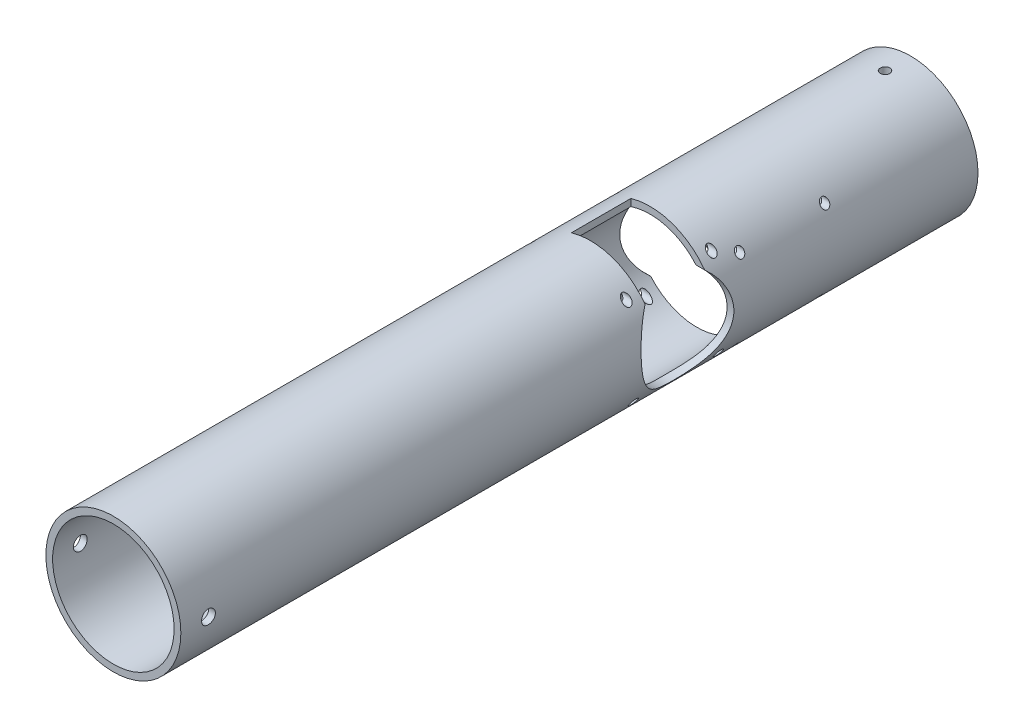
SolidWorks part; units mm, degrees
material "6061 Alloy"
ref_plane "Front Plane" through (0, 0, 0) normal (0, 0, 1) x (1, 0, 0)
ref_plane "Top Plane" through (0, 0, 0) normal (0, 1, 0) x (1, 0, 0)
ref_plane "Right Plane" through (0, 0, 0) normal (1, 0, 0) x (0, 0, -1)
sketch "Sketch1" plane through (0, 0, 0) normal (0, 0, 1) x (1, 0, 0)
  circle A0 centre (0, 0) radius 31.75
  circle A1 centre (0, 0) radius 28.575
  dimension "D1" = 63.5
  dimension "D2" = 57.15
extrude "Boss-Extrude1" add sketch "Sketch1" along normal blind 125 and the other way blind 250 contours A1 | A0 region at (0, 0, 0)
sketch "Sketch2" plane through (0, 0, 0) normal (1, 0, 0) x (0, 0, -1)
  circle A2 centre (163.488, -2) radius 21.75
  dimension "D1" = 43.5
  dimension "D2" = 163.488
  dimension "D3" = 2
extrude "Cut-Extrude1" cut sketch "Sketch2" against normal through all
sketch "Sketch3" plane through (0, 0, 0) normal (1, 0, 0) x (0, 0, -1)
  circle A1 centre (113.45, 2) radius 21.75
  dimension "D1" = 113.45
  dimension "D2" = 43.5
  dimension "D3" = 2
extrude "Cut-Extrude2" cut sketch "Sketch3" along normal through all
sketch "Sketch5" plane through (0, 0, 0) normal (1, 0, 0) x (0, 0, -1)
  line L1 (177.488, -12.75) -> (149.488, -12.75)
  line L2 (177.488, -12.75) -> (177.488, -34.75)
  line L3 (177.488, -34.75) -> (149.488, -34.75)
  line L4 (149.488, -12.75) -> (149.488, -34.75)
  line L5 (177.488, -12.75) -> (149.488, -34.75) construction
  line L6 (177.488, -34.75) -> (149.488, -12.75) construction
  circle A0 centre (163.488, -2) radius 21.75 construction
  circle A1 centre (163.488, -2) radius 21.75 construction
  point P0 (163.488, -23.75)
  dimension "D1" = 28
  dimension "D2" = 22
  dimension "D3" = 163.488
extrude "Cut-Extrude4" cut sketch "Sketch5" against normal through all from offset 9
sketch "Sketch6" plane through (0, 0, 0) normal (1, 0, 0) x (0, 0, -1)
  line L1 (99.45, 34.75) -> (127.45, 34.75)
  line L2 (99.45, 34.75) -> (99.45, 12.75)
  line L3 (99.45, 12.75) -> (127.45, 12.75)
  line L4 (127.45, 34.75) -> (127.45, 12.75)
  line L5 (99.45, 34.75) -> (127.45, 12.75) construction
  line L6 (99.45, 12.75) -> (127.45, 34.75) construction
  circle A0 centre (113.45, 2) radius 21.75 construction
  circle A1 centre (113.45, 2) radius 21.75 construction
  point P0 (113.45, 23.75)
  dimension "D1" = 28
  dimension "D2" = 22
  dimension "D3" = 113.45
extrude "Cut-Extrude5" cut sketch "Sketch6" along normal through all from offset 9 offset against normal yes
sketch "Sketch10" plane through (0, 0, 0) normal (1, 0, 0) x (0, 0, -1)
  line L1 (203.488, 38) -> (123.488, 38)
  line L2 (203.488, 38) -> (203.488, -42)
  line L3 (203.488, -42) -> (123.488, -42)
  line L4 (123.488, 38) -> (123.488, -42)
  line L5 (203.488, 38) -> (123.488, -42) construction
  line L6 (203.488, -42) -> (123.488, 38) construction
  point P0 (163.488, -2)
  dimension "D1" = 80
  dimension "D2" = 80
sketch "Sketch11" plane through (0, 0, 0) normal (1, 0, 0) x (0, 0, -1)
  line L0 (203.488, 38) -> (123.488, -42) construction
  line L1 (203.488, -42) -> (123.488, 38) construction
  circle A0 centre (183.488, 18) radius 2
  circle A1 centre (143.488, 18) radius 2
  circle A2 centre (143.488, -22) radius 2
  circle A3 centre (183.488, -22) radius 2
  dimension "D5" = 4
  dimension "D6" = 4
  dimension "D7" = 4
  dimension "D8" = 4
  dimension "D1" = 20
  dimension "D2" = 20
  dimension "D3" = 20
  dimension "D4" = 20
extrude "Cut-Extrude8" cut sketch "Sketch11" against normal through all both and the other way through all
sketch "Sketch12" plane through (0, 0, 0) normal (1, 0, 0) x (0, 0, -1)
  line L1 (-125, 31.75) -> (-125, -31.75) construction
  circle A0 centre (-136, 0) radius 3.25
  circle A1 centre (-112, 0) radius 3.25
  dimension "D1" = 6.5
  dimension "D2" = 6.5
  dimension "D3" = 24
  dimension "D4" = 13
extrude "Cut-Extrude10" cut sketch "Sketch12" against normal through all both and the other way through all
sketch "Sketch13" plane through (0, 0, 0) normal (0, 1, 0) x (1, 0, 0)
  line L0 (0, -55) -> (0, 55) construction
  line L1 (28.575, 250) -> (-28.575, 250) construction
  circle A0 centre (0, 238) radius 2.25
  dimension "D2" = 4.5
  dimension "D1" = 12
extrude "Cut-Extrude11" cut sketch "Sketch13" against normal through all both and the other way through all
sketch "Sketch14" plane through (0, 0, 0) normal (1, 0, 0) x (0, 0, -1)
  line L1 (88.45, 27) -> (138.45, 27)
  line L2 (88.45, 27) -> (88.45, -23)
  line L3 (88.45, -23) -> (138.45, -23)
  line L4 (138.45, 27) -> (138.45, -23)
  line L5 (88.45, 27) -> (138.45, -23) construction
  line L6 (88.45, -23) -> (138.45, 27) construction
  circle A0 centre (93.45, 22) radius 2
  circle A1 centre (133.45, 22) radius 2
  circle A2 centre (133.45, -18) radius 2
  circle A3 centre (93.45, -18) radius 2
  point P0 (113.45, 2)
  dimension "D4" = 4
  dimension "D5" = 4
  dimension "D6" = 4
  dimension "D7" = 4
  dimension "D1" = 50
  dimension "D2" = 50
  dimension "D3" = 20
  dimension "D8" = 20
  dimension "D9" = 20
  dimension "D10" = 20
sketch "Sketch15" plane through (0, 0, 0) normal (1, 0, 0) x (0, 0, -1)
  circle A0 centre (93.45, 22) radius 2
  circle A1 centre (133.45, 22) radius 2
  circle A2 centre (133.45, -18) radius 2
  circle A3 centre (93.45, -18) radius 2
extrude "Cut-Extrude12" cut sketch "Sketch15" against normal through all and the other way through all
